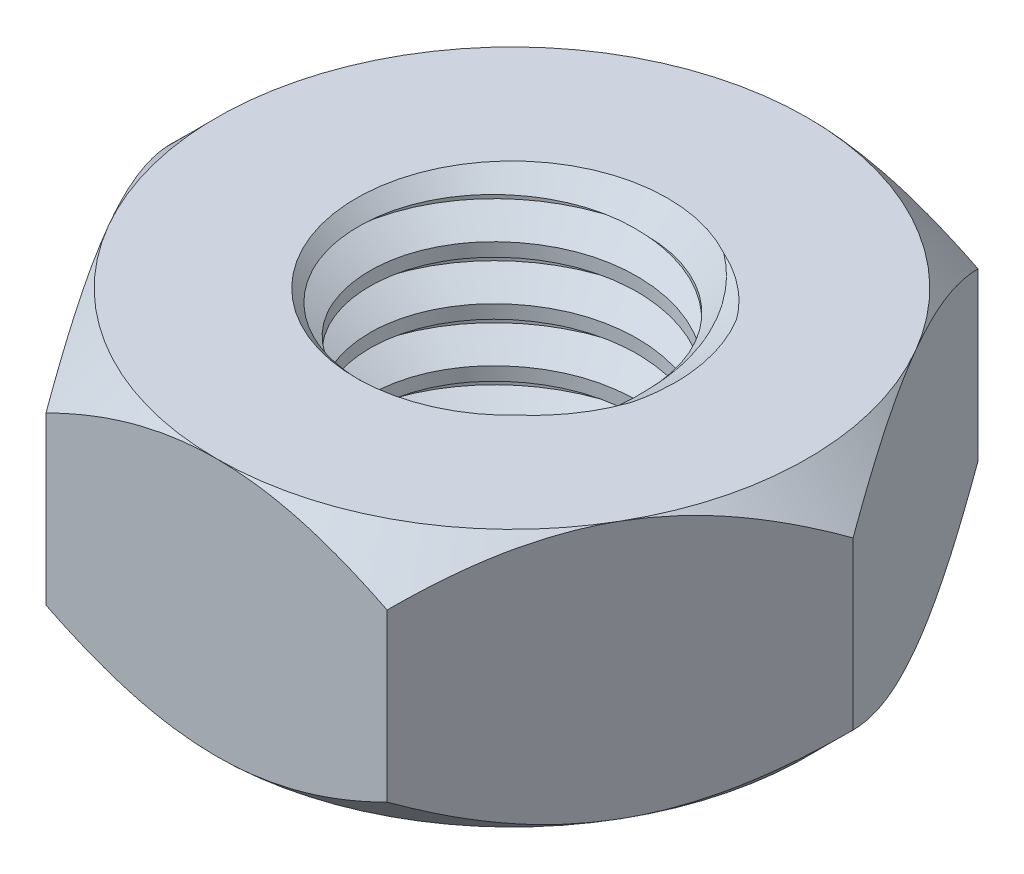
SolidWorks part; units mm, degrees
ref_plane "Front Plane" through (0, 0, 0) normal (0, 0, 1) x (1, 0, 0)
ref_plane "Top Plane" through (0, 0, 0) normal (0, 1, 0) x (1, 0, 0)
ref_plane "Right Plane" through (0, 0, 0) normal (1, 0, 0) x (0, 0, -1)
sketch "Sketch1" plane through (0, 0, 0) normal (0, 1, 0) x (1, 0, 0)
  line L1 (3.1754, 0) -> (1.5877, 2.75)
  line L2 (1.5877, 2.75) -> (-1.5877, 2.75)
  line L3 (-1.5877, 2.75) -> (-3.1754, 0)
  line L4 (-3.1754, 0) -> (-1.5877, -2.75)
  line L5 (-1.5877, -2.75) -> (1.5877, -2.75)
  line L6 (1.5877, -2.75) -> (3.1754, 0)
  circle A0 centre (0, 0) radius 2.75 construction
  dimension "D1" = 5.5
extrude "Boss-Extrude1" add sketch "Sketch1" along normal blind 2.4
sketch "Sketch2" plane through (0, 2.4, 0) normal (0, 1, 0) x (1, 0, 0)
  circle A0 centre (0, 0) radius 2.75
extrude "Cut-Extrude1" cut sketch "Sketch2" against normal through all draft 45 flip side to cut contours A0 region at (0, 2.4, 0)
sketch "Sketch3" plane through (0, 0, 0) normal (0, -1, 0) x (1, 0, 0)
  circle A0 centre (0, 0) radius 2.75
extrude "Cut-Extrude2" cut sketch "Sketch3" against normal through all draft 45 flip side to cut contours A0 region at (0, 0, 0)
sketch "Sketch4" plane through (0, 2.4, 0) normal (0, 1, 0) x (1, 0, 0)
  circle A0 centre (0, 0) radius 1.25
  dimension "D1" = 2.5
extrude "Cut-Extrude3" cut sketch "Sketch4" against normal through all
chamfer "Chamfer1" distance 0.2 angle 45 2 edges at (0, 2.4, 1.25) (0, 0, 1.25)
thread "Thread1" pitch 0.5 method cut profile "Thread Profile1" start angle 0, offset 1, length 0, pitch 0.5, diameter 2.5
ref_plane "Plane1" through (1.25, -0.8, 0) normal (0, 0, 1) x (1, 0, 0)
sketch "Thread Profile1" plane through (1.25, -0.8, 0) normal (0, 0, 1) x (1, 0, 0)
  line L0 (0, 0) -> (0, 0.5) construction
  line L1 (0, 0) -> (0.2706, 0.1562)
  line L2 (0.2706, 0.1562) -> (0.2706, 0.2187)
  line L3 (0.2706, 0.2187) -> (0, 0.375)
  line L4 (0.2706, 0.1875) -> (0, 0.1875) construction
  line L11 (0, 0) -> (0, 0.375)
  point P2 (0, 0)
  dimension "Pitch" = 0.5
  dimension "Profile_Angle" = 60
  dimension "Profile_Land" = 0.0625
  dimension "Profile_Height" = 0.2706
